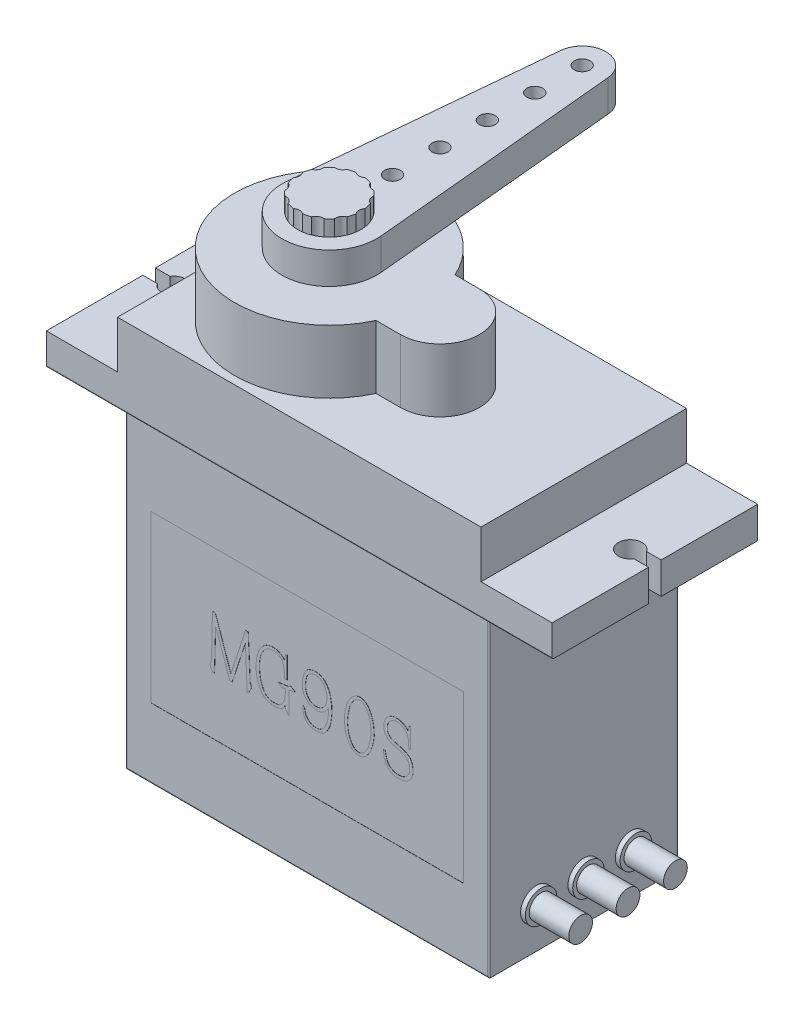
SolidWorks part; units mm, degrees
ref_plane "前视基准面" through (0, 0, 0) normal (0, 0, 1) x (1, 0, 0)
ref_plane "上视基准面" through (0, 0, 0) normal (0, 1, 0) x (1, 0, 0)
ref_plane "右视基准面" through (0, 0, 0) normal (1, 0, 0) x (0, 0, -1)
sketch "草图1" plane through (0, 0, 0) normal (0, 1, 0) x (1, 0, 0)
  line L1 (-11.5, 6) -> (11.5, 6)
  line L2 (-11.5, 6) -> (-11.5, -6)
  line L3 (-11.5, -6) -> (11.5, -6)
  line L4 (11.5, 6) -> (11.5, -6)
  line L5 (-11.5, 6) -> (11.5, -6) construction
  line L6 (-11.5, -6) -> (11.5, 6) construction
  point P0 (0, 0)
  dimension "D1" = 12
  dimension "D2" = 23
extrude "凸台-拉伸1" add sketch "草图1" along normal blind 20
sketch "草图2" plane through (0, 20, 0) normal (0, 1, 0) x (1, 0, 0)
  line L1 (-16, 6.5) -> (16, 6.5)
  line L2 (-16, 6.5) -> (-16, -6.5)
  line L3 (-16, -6.5) -> (16, -6.5)
  line L4 (16, 6.5) -> (16, -6.5)
  line L5 (-16, 6.5) -> (16, -6.5) construction
  line L6 (-16, -6.5) -> (16, 6.5) construction
  point P0 (0, 0)
  dimension "D1" = 13
  dimension "D2" = 32
extrude "凸台-拉伸2" add sketch "草图2" along normal blind 2
sketch "草图3" plane through (0, 22, 0) normal (0, 1, 0) x (1, 0, 0)
  line L1 (-11.5, 6.5) -> (11.5, 6.5)
  line L2 (-11.5, 6.5) -> (-11.5, -6.5)
  line L3 (-11.5, -6.5) -> (11.5, -6.5)
  line L4 (11.5, 6.5) -> (11.5, -6.5)
  line L5 (-11.5, 6.5) -> (11.5, -6.5) construction
  line L6 (-11.5, -6.5) -> (11.5, 6.5) construction
  point P0 (0, 0)
  dimension "D1" = 13
  dimension "D2" = 23
extrude "凸台-拉伸3" add sketch "草图3" along normal blind 3
sketch "草图4" plane through (0, 22, 0) normal (0, 1, 0) x (1, 0, 0)
  line L0 (-16, 0.4) -> (-15.0743, 0.4)
  line L1 (-16, 6.5) -> (-16, -6.5) construction
  line L2 (-16.3919, 0) -> (-13.0929, 0) construction
  line L3 (-16, -0.4) -> (-15.0743, -0.4)
  line L4 (0, 7.1501) -> (0, -7.6691) construction
  line L5 (-16, 0.4) -> (-15.0743, 0.4)
  line L6 (-16, -0.4) -> (-15.0743, -0.4)
  line L7 (16.3919, 0) -> (13.0929, 0) construction
  line L8 (16, -0.4) -> (15.0743, -0.4)
  line L9 (16, 0.4) -> (15.0743, 0.4)
  line L10 (16, -0.4) -> (15.0743, -0.4)
  line L11 (16, 0.4) -> (15.0743, 0.4)
  line L12 (-16, 0.4) -> (-17.2057, 0.4)
  line L13 (-17.2057, 0.4) -> (-17.2057, -0.4824)
  line L14 (-17.2057, -0.4824) -> (-16, -0.4)
  line L15 (16, 0.4) -> (17.5704, 0.4)
  line L16 (17.5704, 0.4) -> (17.5704, -0.5598)
  line L17 (17.5704, -0.5598) -> (16, -0.4)
  circle A0 centre (-14.4399, 0) radius 0.75
  circle A1 centre (14.4399, 0) radius 0.75
  line M6 (-16, 6.5) -> (-16, -6.5)
  dimension "D1" = 1.5
  dimension "D2" = 0.4
extrude "切除-拉伸1" cut sketch "草图4" against normal blind 5 contours A0 | A0 L0 L3 M6 | L13 L14 L12 M6 | A1 | L9 A1 L8 L17 L16 L15 region at (-16.6127, 22, 0.0209) region at (-15.5756, 22, 0) region at (-14.4399, 22, 0) region at (16.403, 22, 0.0276) region at (14.4399, 22, 0)
sketch "草图5" plane through (0, 25, 0) normal (0, 1, 0) x (1, 0, 0)
  line L0 (2.3993, 2.5) -> (0.8537, 2.5)
  line L1 (2.3993, -2.5) -> (0.8537, -2.5)
  circle A0 centre (-4.6007, 0) radius 6
  circle A1 centre (2.3993, 0) radius 2.5
  dimension "D1" = 12
  dimension "D2" = 5
  dimension "D3" = 7
extrude "凸台-拉伸4" add sketch "草图5" along normal blind 4 contours A1 L0 A0 | A1 A0 | A0 A1 | A1 A0 L1 | A1 A0 region at (1.3003, 25, -2.3763) region at (2.8807, 25, 0) region at (-4.8135, 25, 0) region at (0.7115, 25, 0) region at (1.3003, 25, 2.3763)
sketch "草图6" plane through (0, 29, 0) normal (0, 1, 0) x (1, 0, 0)
  circle A0 centre (-4.6007, 0) radius 2
  dimension "D1" = 4
extrude "凸台-拉伸5" add sketch "草图6" along normal blind 3
sketch "草图7" plane through (0, 32, 0) normal (0, 1, 0) x (1, 0, 0)
  circle A0 centre (-4.6014, 2.331) radius 0.4517
extrude "切除-拉伸2" cut sketch "草图7" against normal blind 3
pattern_circular "阵列(圆周)1" count 12 over 360 about axis through (-4.6007, 32, 0) along (0, 1, 0) of "切除-拉伸2"
sketch "草图9" plane through (0, 29, 0) normal (0, 1, 0) x (1, 0, 0)
  line L0 (-6.0941, 16.1406) -> (-7.5875, 0.2813)
  line L1 (-4.6007, 0) -> (-4.6007, 4.4473) construction
  line L2 (-3.1073, 16.1406) -> (-1.6139, 0.2813)
  circle A0 centre (-4.6007, 0) radius 2
  circle A1 centre (-4.6007, 0) radius 3
  circle A2 centre (-4.6007, 16) radius 1.5
  circle A3 centre (-4.6007, 16) radius 0.5
  circle A4 centre (-4.6007, 13) radius 0.5
  circle A5 centre (-4.6007, 10) radius 0.5
  circle A6 centre (-4.6007, 7) radius 0.5
  circle A7 centre (-4.6007, 4) radius 0.5
  arc M9 (-6.5805, 0.2834) -> (-6.4574, 0.7434) centre (-4.6007, 0) cw
  arc M11 (-6.1735, 1.2353) -> (-5.837, 1.5721) centre (-4.6007, 0) cw
  arc M13 (-5.3452, 1.8563) -> (-4.8853, 1.9796) centre (-4.6007, 0) cw
  arc M15 (-4.3173, 1.9798) -> (-3.8573, 1.8567) centre (-4.6007, 0) cw
  arc M17 (-3.3653, 1.5729) -> (-3.0285, 1.2363) centre (-4.6007, 0) cw
  arc M19 (-2.7444, 0.7445) -> (-2.621, 0.2846) centre (-4.6007, 0) cw
  arc M21 (-2.6208, -0.2834) -> (-2.7439, -0.7434) centre (-4.6007, 0) cw
  arc M23 (-3.0278, -1.2353) -> (-3.3644, -1.5721) centre (-4.6007, 0) cw
  arc M25 (-3.8562, -1.8563) -> (-4.3161, -1.9796) centre (-4.6007, 0) cw
  arc M27 (-4.8841, -1.9798) -> (-5.344, -1.8567) centre (-4.6007, 0) cw
  arc M29 (-5.836, -1.5729) -> (-6.1728, -1.2363) centre (-4.6007, 0) cw
  arc M31 (-6.4569, -0.7445) -> (-6.5803, -0.2846) centre (-4.6007, 0) cw
  arc M36 (0.8537, 2.5) -> (0.8537, -2.5) centre (-4.6007, 0) ccw
  dimension "D1" = 4
  dimension "D3" = 3
  dimension "D4" = 16
  dimension "D5" = 1
  dimension "D6" = 5
  dimension "D2" = 1
extrude "凸台-拉伸6" add sketch "草图9" along normal blind 2 contours A2 A3 | A2 L0 L2 A6 A5 A4 M36 | A1 L2 L0 A7 M36 | A0 A1 M25 M27 M29 M31 M9 M11 M13 M15 M17 M19 M21 M23 region at (-4.6766, 29, -14.3838) region at (-4.6007, 29, -17.4576) region at (-4.6007, 29, -5.9173) region at (-4.6007, 29, -2.9151)
fillet "圆角1" radius 0.1 11 edges at (11.5, 20, 0) (-11.5, 20, 0) (-11.5, 10, 6) (0, 20, 6) (11.5, 10, 6) (0, 0, 6) (11.5, 10, -6) (-11.5, 10, -6) (0, 20, -6.5) (0, 20, -6) (0, 20, 6.5)
sketch "草图10" plane through (0, 0, -6) normal (0, 0, -1) x (-1, 0, 0)
  line L1 (-9.8789, 14.9195) -> (9.8789, 14.9195)
  line L2 (-9.8789, 14.9195) -> (-9.8789, 4.4232)
  line L3 (-9.8789, 4.4232) -> (9.8789, 4.4232)
  line L4 (9.8789, 14.9195) -> (9.8789, 4.4232)
  line L5 (-9.8789, 14.9195) -> (9.8789, 4.4232) construction
  line L6 (-9.8789, 4.4232) -> (9.8789, 14.9195) construction
  point P0 (0, 9.6713)
extrude "切除-拉伸3" cut sketch "草图10" against normal blind 0.01
sketch "草图11" plane through (0, 0, -5.99) normal (0, 0, -1) x (-1, 0, 0)
  text T0 "MG90S" font "汉仪长仿宋体" height 3.5
extrude "凸台-拉伸7" add sketch "草图11" along normal blind 0.01
mirror "镜向1" about plane through (0, 0, 0) normal (0, 0, 1) of "切除-拉伸3"
sketch "草图12" plane through (0, 0, 5.99) normal (0, 0, 1) x (1, 0, 0)
  text T0 "MG90S" font "汉仪长仿宋体" height 3.5
extrude "凸台-拉伸8" add sketch "草图12" along normal blind 0.01
sketch "草图13" plane through (11.5, 0, 0) normal (1, 0, 0) x (0, 0, -1)
  circle A0 centre (0, 2.615) radius 1
  circle A1 centre (3, 2.615) radius 1
  circle A2 centre (-3, 2.615) radius 1
  dimension "D1" = 2
  dimension "D2" = 2
  dimension "D3" = 2
  dimension "D4" = 3
  dimension "D5" = 3
extrude "凸台-拉伸9" add sketch "草图13" along normal blind 0.3
sketch "草图14" plane through (11.8, 0, 0) normal (1, 0, 0) x (0, 0, -1)
  circle A0 centre (-3, 2.615) radius 0.75
  circle A1 centre (0, 2.615) radius 0.75
  circle A2 centre (3, 2.615) radius 0.75
  dimension "D1" = 1.5
  dimension "D2" = 1.5
  dimension "D3" = 1.5
extrude "凸台-拉伸10" add sketch "草图14" along normal blind 2.5
